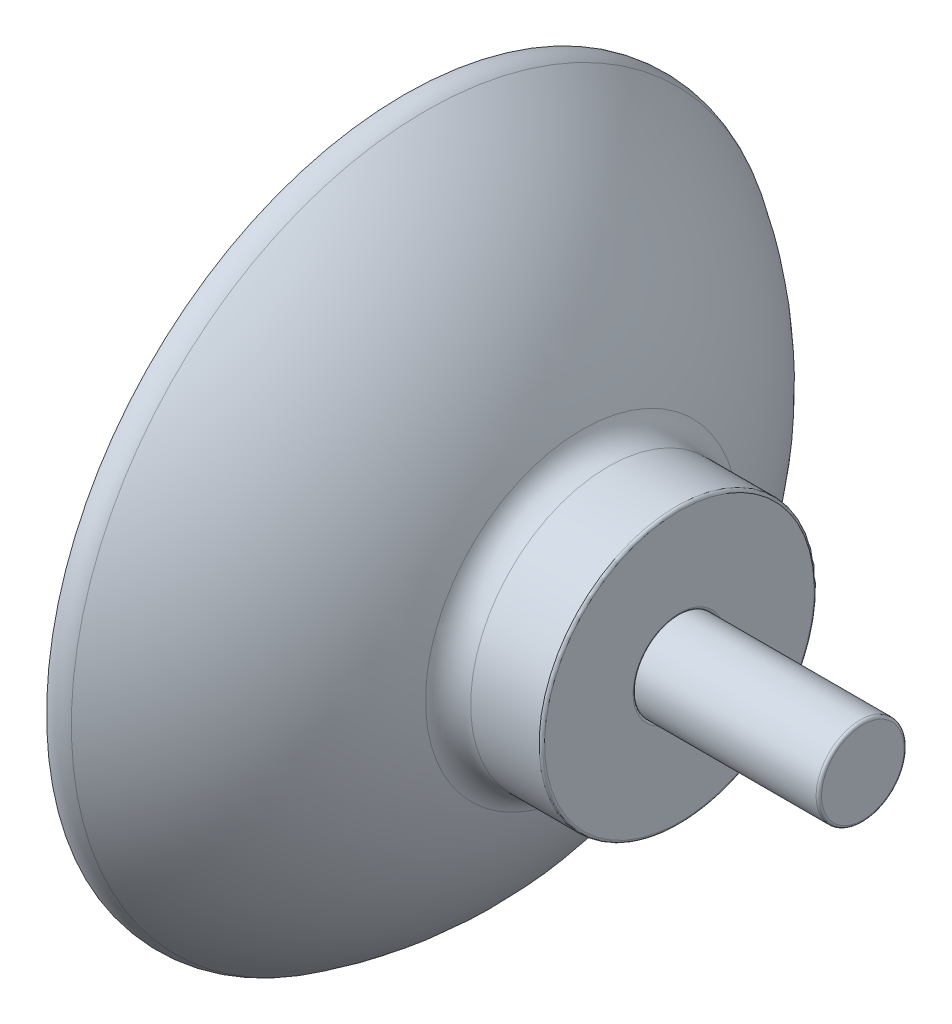
SolidWorks part; units mm, degrees
material "Malleable Cast Iron"
ref_plane "Front" through (0, 0, 0) normal (0, 0, 1) x (1, 0, 0)
ref_plane "Top" through (0, 0, 0) normal (0, 1, 0) x (1, 0, 0)
ref_plane "Right" through (0, 0, 0) normal (1, 0, 0) x (0, 0, -1)
sketch "Sketch1" plane through (0, 0, 0) normal (0, 0, 1) x (1, 0, 0)
  line L0 (0, 0) -> (-10, 0) construction
  line L1 (0, 0) -> (5, 0) construction
  line L2 (0, 0) -> (0, 7.5)
  line L3 (0, 7.5) -> (5, 7.5)
  line L4 (5, 0) -> (5, 7.5)
  line L5 (2, 0) -> (4, 0) construction
  line L6 (2, 0) -> (2, 4.75)
  line L7 (2, 4.75) -> (4, 4.75)
  line L8 (4, 0) -> (4, 4.75)
  line L9 (-10, 0) -> (-10, 20) construction
  line L10 (-10, 20) -> (-10, 19.5)
  line L11 (0, 0) -> (2, 0)
  line L12 (4, 0) -> (5, 0)
  line L13 (4, 2.375) -> (5, 2.375)
  arc A0 (-10, 20) -> (0, 7.5) centre (-19.3122, 2.3002) cw
  arc A1 (-10, 19.5) -> (0, 4) centre (-21.7836, 0.9219) cw
  dimension "D8" = 20
  dimension "D10" = 22
  dimension "D1" = 5
  dimension "D2" = 7.5
  dimension "D3" = 2
  dimension "D4" = 1
  dimension "D5" = 4.75
  dimension "D6" = 10
  dimension "D7" = 20
  dimension "D9" = 0.5
  dimension "D11" = 3.5
revolve "Revolve1" add sketch "Sketch1" angle 360 about L0 region at (0.0901, 2, 0) region at (-3.1385, 12.951, 0)
fillet "Fillet1" radius 0.15 1 edges at (5, 7.5, 0)
fillet "Fillet2" radius 0.15 1 edges at (5, 2.375, 0)
fillet "Fillet3" radius 1.5 2 edges at (-10, 20, 0) (0, 7.5, 0)
sketch "Sketch2" plane through (0, 0, 0) normal (0, 1, 0) x (1, 0, 0)
  line L0 (2, 4.75) -> (2, 0)
  line L1 (2, -4.75) -> (2, 4.75) construction
  line L2 (2, 0) -> (15, 0)
  line L3 (15, 0) -> (15, 2.4)
  line L4 (15, 2.4) -> (4, 2.4)
  line L8 (4, 4.75) -> (4, -4.75) construction
  line L9 (4, 2.4) -> (4, 4.75)
  line L10 (4, 4.75) -> (2, 4.75)
  line L11 (5, -7.35) -> (5, 7.35) construction
  point P16 (15, 1.2)
  dimension "D1" = 2.35
  dimension "D2" = 10
  dimension "D3" = 2.4
revolve "Revolve2" add sketch "Sketch2" angle 360 about L2
fillet "Fillet4" radius 0.15 1 edges at (15, 0, 2.4)
